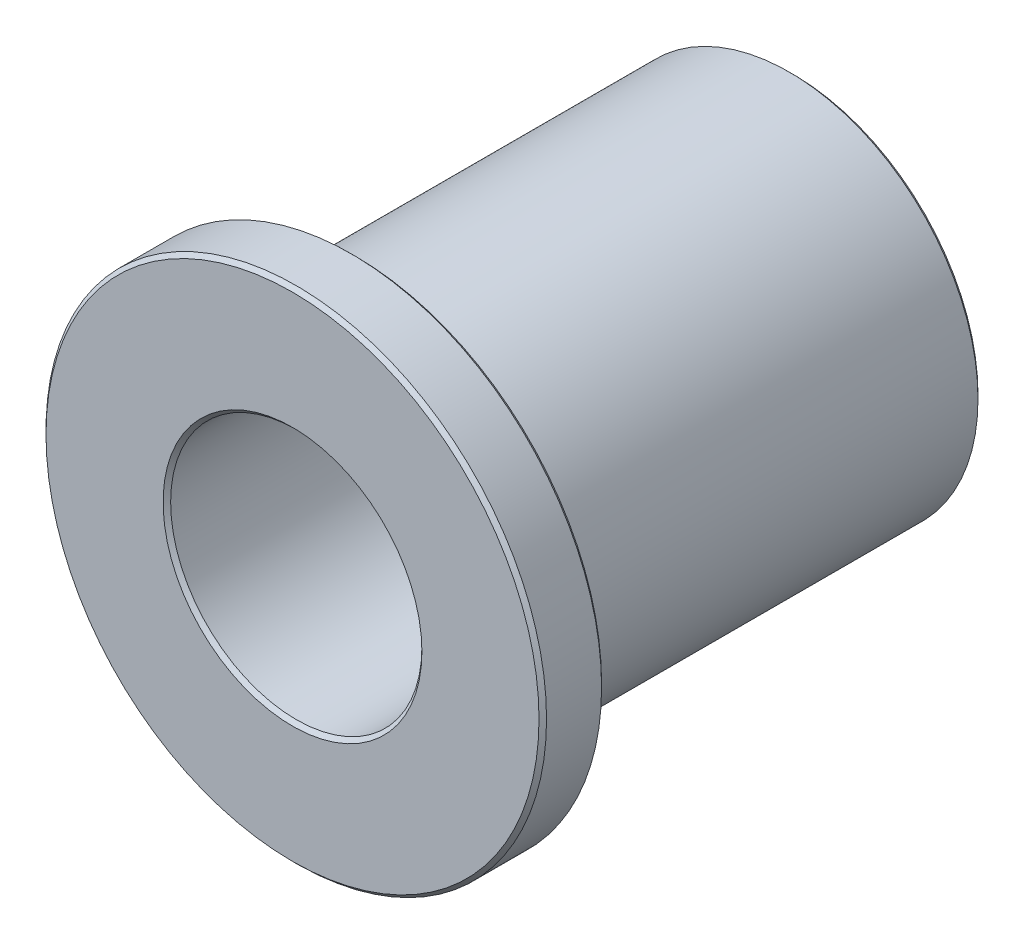
SolidWorks part; units mm, degrees
ref_plane "Front" through (0, 0, 0) normal (0, 0, 1) x (1, 0, 0)
ref_plane "Top" through (0, 0, 0) normal (0, 1, 0) x (1, 0, 0)
ref_plane "Right" through (0, 0, 0) normal (1, 0, 0) x (0, 0, -1)
sketch "Sketch1" plane through (0, 0, 0) normal (0, 0, 1) x (1, 0, 0)
  circle A0 centre (0, 0) radius 3.1877
  circle A1 centre (0, 0) radius 4.7879
  circle A2 centre (0, 0) radius 6.35
  dimension "ID" = 6.3754
  dimension "OD" = 9.5758
  dimension "Flange OD" = 12.7
sketch "Sketch2" plane through (0, 0, 0) normal (1, 0, 0) x (0, 0, -1)
  line L0 (-6.35, -6.35) -> (6.35, -6.35) construction
  line L1 (0, 6.35) -> (0, -6.35) construction
  line L3 (-4.7625, 4.7879) -> (6.35, 4.7879) construction
  point P3 (0, -6.35)
  point P7 (0, 4.7879)
  point P9 (-4.7625, -6.35)
  point P10 (-6.35, 6.35)
  point P23 (0, 6.35)
  dimension "Flange Thickness" = 1.5875
  dimension "Length" = 12.7
sketch "Sketch3" plane through (0, 0, 0) normal (0, 0, 1) x (1, 0, 0)
  circle A0 centre (0, 0) radius 6.35 construction
  circle A1 centre (0, 0) radius 6.35
  circle A2 centre (0, 0) radius 3.1877 construction
  circle A3 centre (0, 0) radius 3.1877
extrude "Boss-Extrude1" add sketch "Sketch3" against normal up to vertex (-4.7625 mm away) from vertex up to point (0, -6.35, 4.7625) starting at point (0, -6.35, 6.35)
sketch "Sketch4" plane through (0, 0, 0) normal (0, 0, 1) x (1, 0, 0)
  circle A0 centre (0, 0) radius 3.1877 construction
  circle A1 centre (0, 0) radius 4.7879 construction
  circle A2 centre (0, 0) radius 3.1877
  circle A3 centre (0, 0) radius 4.7879
extrude "Boss-Extrude2" add sketch "Sketch4" against normal up to vertex (6.35 mm away) from vertex up to point (0, 4.7879, -6.35) starting at point (0, -6.35, 4.7625)
chamfer "Chamfer1" distance 0.0956 angle 45 6 edges at (3.1877, 0, 6.35) (6.35, 0, 6.35) (6.35, 0, 4.7625) (4.7879, 0, 4.7625) (3.1877, 0, -6.35) (4.7879, 0, -6.35)
equation "\"D1@Chamfer1\"=\"ID@Sketch1\"*0.015"
